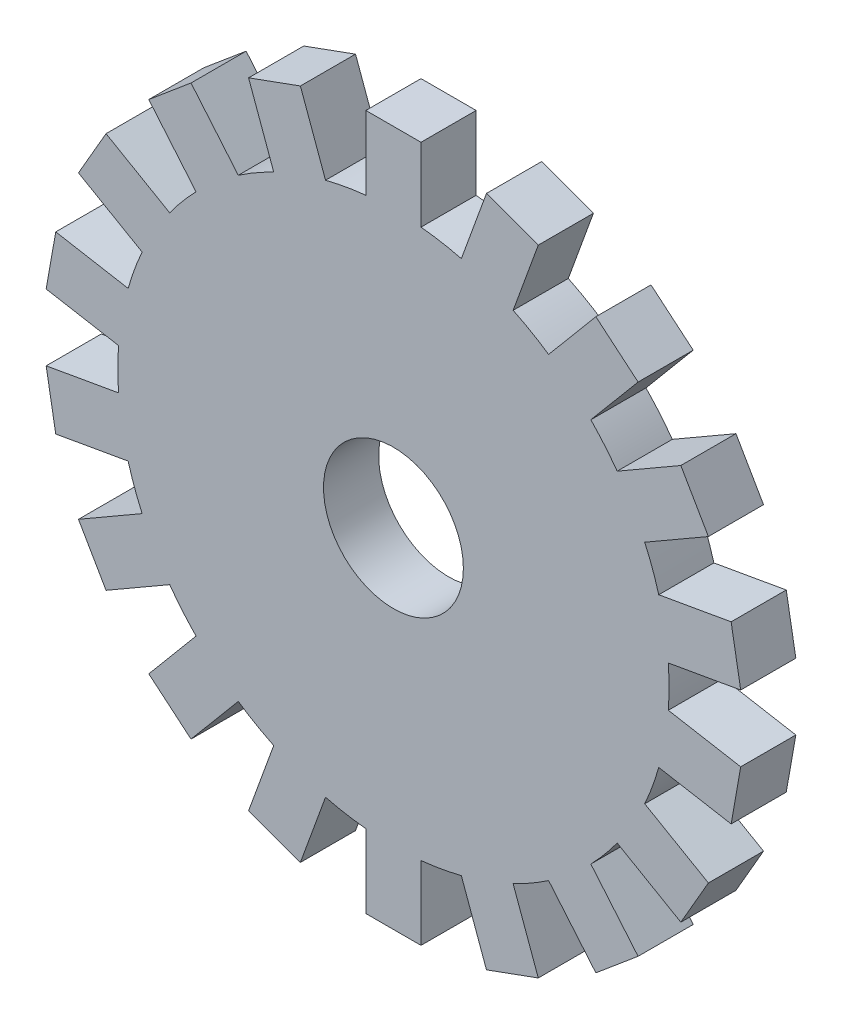
SolidWorks part; units mm, degrees
ref_plane "Front Plane" through (0, 0, 0) normal (0, 0, 1) x (1, 0, 0)
ref_plane "Top Plane" through (0, 0, 0) normal (0, 1, 0) x (1, 0, 0)
ref_plane "Right Plane" through (0, 0, 0) normal (1, 0, 0) x (0, 0, -1)
sketch "Sketch1" plane through (0, 0, 0) normal (0, 0, 1) x (1, 0, 0)
  line L0 (0, 0) -> (0, 15) construction
  line L1 (-1.5, 14.9248) -> (-1.5, 18.9248)
  line L2 (-1.5, 18.9248) -> (1.5, 18.9248)
  line L3 (1.5, 14.9248) -> (1.5, 18.9248)
  circle A0 centre (0, 0) radius 15
  circle A1 centre (0, 0) radius 3.8058
  point P8 (0, 18.9248)
  dimension "D2" = 30
  dimension "D1" = 3
  dimension "D3" = 4
extrude "Boss-Extrude1" add sketch "Sketch1" along normal mid plane 3 contours A0 region at (0, 14.5757, 0)
extrude "Boss-Extrude2" add sketch "Sketch1<3>" along normal mid plane 3 contours A0 L3 L2 L1 region at (0, 16.9498, 0)
sketch "Sketch1<3>" plane through (0, 0, 0) normal (0, 0, 1) x (1, 0, 0) same geometry as "Sketch1"
ref_axis "Axis1" through (0, 0, 13.2194) along (0, 0, -1)
pattern_circular "CirPattern1" count 18 over 360 about axis through (0, 0, 13.2194) along (0, 0, -1) of "Boss-Extrude2"
